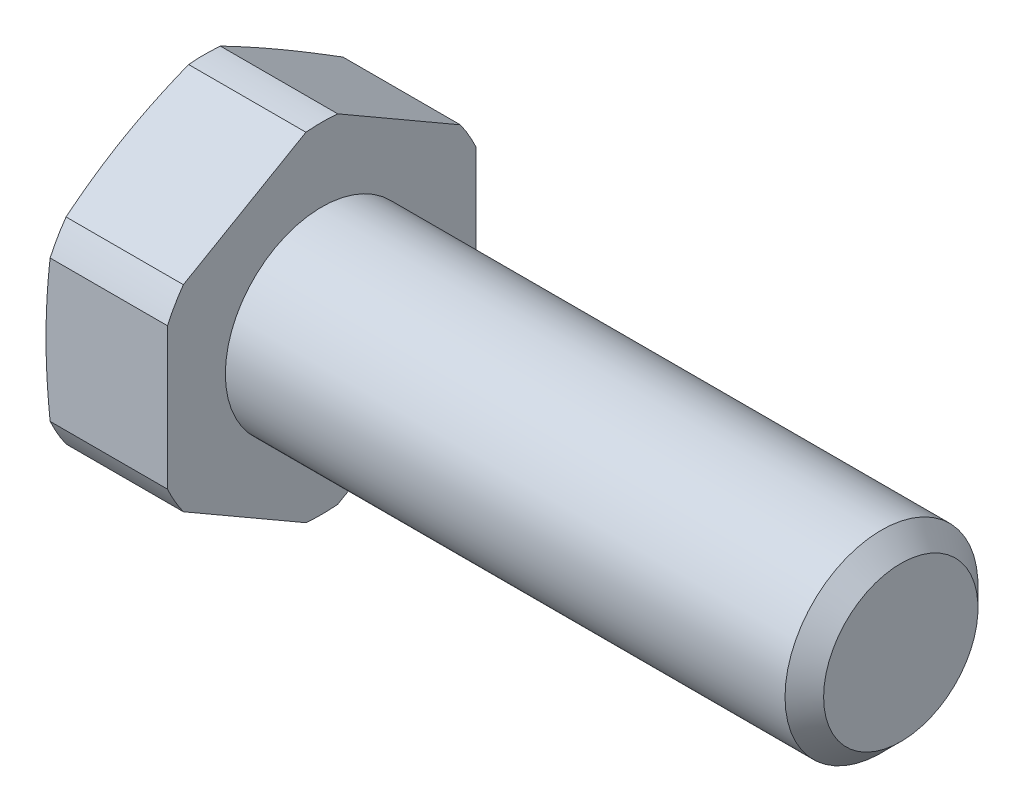
SolidWorks part; units mm, degrees
material "AISI 1020"
ref_plane "Спереди" through (0, 0, 0) normal (0, 0, 1) x (1, 0, 0)
ref_plane "Сверху" through (0, 0, 0) normal (0, 1, 0) x (1, 0, 0)
ref_plane "Справа" through (0, 0, 0) normal (1, 0, 0) x (0, 0, -1)
sketch "Эскиз1" plane through (0, 0, 0) normal (0, 0, 1) x (1, 0, 0)
  line L0 (-1000, 0) -> (49000, 0) construction
  line L1 (-6.4, 0) -> (-6.4, 7.6)
  line L2 (-6.4, 7.6) -> (-6.0785, 8.8)
  line L3 (-6.0785, 8.8) -> (0, 8.8)
  line L4 (0, 8.8) -> (0, 5)
  line L5 (0, 5) -> (29, 5)
  line L6 (30, 4) -> (30, 0)
  line L7 (30, 5) -> (30.75, 6.299) construction
  line L8 (30.75, 6.299) -> (31.5, 5) construction
  line L9 (31.5, 5) -> (30, 5) construction
  line L10 (30.75, 6.299) -> (30.75, 5) construction
  line L11 (30.75, 6.299) -> (0.75, 6.299) construction
  line L12 (29, 5) -> (30, 4)
  line L13 (30, 5) -> (29.5, 4.5) construction
  line L14 (-6.4, 7.6) -> (-22.4, 7.6) construction
  line L15 (-6.4, 0) -> (30, 0)
  dimension "D1" = 1
  dimension "D2" = 15
revolve "Повернуть1" add sketch "Эскиз1" angle 360 about L0
cosmetic thread "Условное изображение резьбы1" parameters "D1"=30, "D2"=7.4019
sketch "Эскиз2" plane through (-6.4, 0, 0) normal (-1, 0, 0) x (0, 0, 1)
  line L1 (0, 9.2376) -> (-8, 4.6188)
  line L2 (-8, 4.6188) -> (-8, -4.6188)
  line L3 (-8, -4.6188) -> (0, -9.2376)
  line L4 (0, -9.2376) -> (8, -4.6188)
  line L5 (8, -4.6188) -> (8, 4.6188)
  line L6 (8, 4.6188) -> (0, 9.2376)
  circle A0 centre (0, 0) radius 8 construction
  dimension "D1" = 16
extrude "Вырез-Вытянуть1" cut sketch "Эскиз2" against normal up to surface (36.4 mm away) flip side to cut up to face at (30, 0, 4)
equation "\"D1@Эскиз1\"=\"_d_@Эскиз1\"/10"
equation "\"D@Эскиз1\"=\"S_@Эскиз1\"*0.95"
equation "\"D1@Эскиз2\"=\"S_@Эскиз1\""
equation "\"D1@Условное изображение резьбы1\"=\"b_@Эскиз1\""
equation "\"D2@Условное изображение резьбы1\"=\"_d_@Эскиз1\"-\"dr@Эскиз1\"*2"
